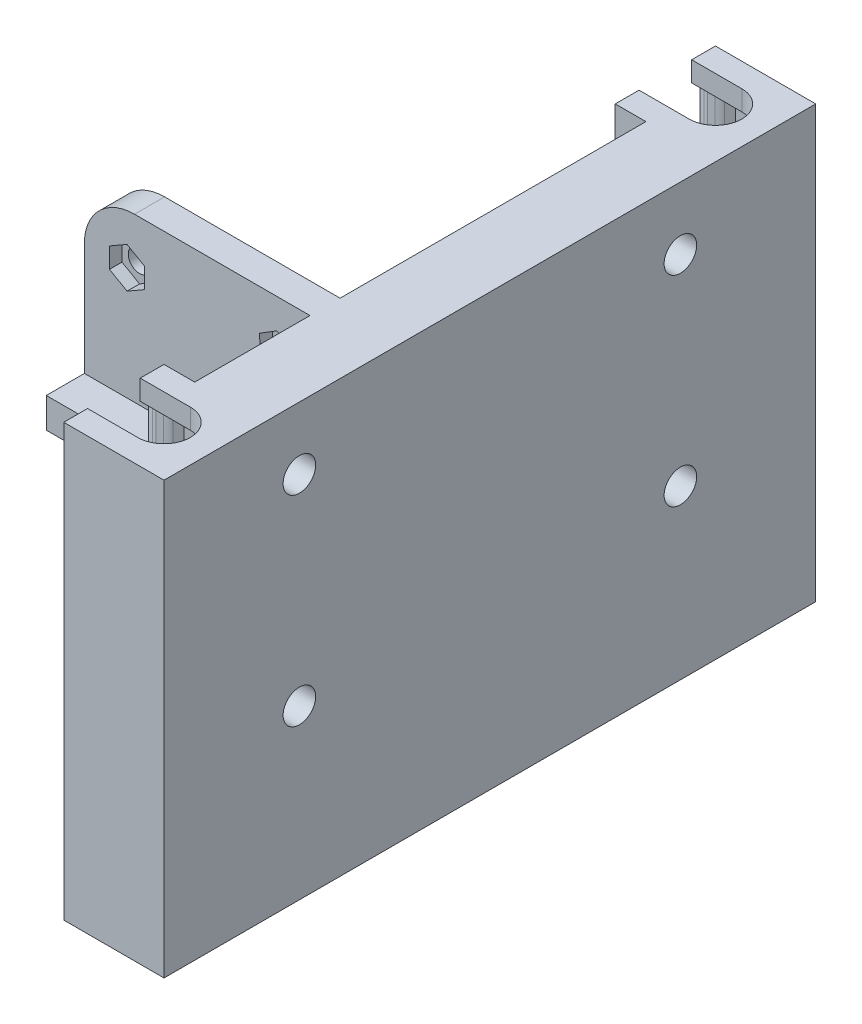
SolidWorks part; units mm, degrees
ref_plane "Front Plane" through (0, 0, 0) normal (0, 0, 1) x (1, 0, 0)
ref_plane "Top Plane" through (0, 0, 0) normal (0, 1, 0) x (1, 0, 0)
ref_plane "Right Plane" through (0, 0, 0) normal (1, 0, 0) x (0, 0, -1)
sketch "Sketch1" plane through (0, 0, 0) normal (0, 1, 0) x (1, 0, 0)
  line L21 (-7.527, -41.3041) -> (-7.527, 88.6959)
  line L22 (-7.527, 88.6959) -> (-27.527, 88.6959)
  line L23 (-27.527, 88.6959) -> (-27.527, 68.6959)
  line L24 (-27.527, 68.6959) -> (-21.4063, 68.6959)
  line L25 (-21.4063, 68.6959) -> (-21.4063, -21.3041)
  line L26 (-21.4063, -21.3041) -> (-27.527, -21.3041)
  line L27 (-27.527, -21.3041) -> (-27.527, -41.3041)
  line L28 (-27.527, -41.3041) -> (-7.527, -41.3041)
  dimension "D1" = 130
  dimension "D2" = 20
  dimension "D3" = 20
extrude "Boss-Extrude1" add sketch "Sketch1" along normal blind 86
sketch "Sketch2" plane through (0, 86, 0) normal (0, 1, 0) x (1, 0, 0)
  line L0 (-17.527, 83.9459) -> (-27.527, 83.9459)
  line L1 (-27.527, 88.6959) -> (-27.527, 68.6959) construction
  line L2 (-17.527, 73.4459) -> (-27.527, 73.4459)
  line L3 (-27.527, 83.9459) -> (-27.527, 73.4459)
  line L4 (-17.527, -26.0541) -> (-27.527, -26.0541)
  line L5 (-27.527, -21.3041) -> (-27.527, -41.3041) construction
  line L6 (-27.527, -26.0541) -> (-27.527, -36.5541)
  line L7 (-27.527, -36.5541) -> (-17.527, -36.5541)
  line L8 (-17.527, -31.3041) -> (-17.527, 105.8048) construction
  line L9 (-27.527, 78.6959) -> (0, 78.6959) construction
  arc A2 (-17.527, -36.5541) -> (-17.527, -26.0541) centre (-17.527, -31.3041) ccw
  arc A3 (-17.527, 73.4459) -> (-17.527, 83.9459) centre (-17.527, 78.6959) ccw
  point P14 (-27.527, 78.6959)
  dimension "D1" = 10.5
  dimension "D2" = 10.5
extrude "Cut-Extrude1" cut sketch "Sketch2" against normal up to next
sketch "Sketch3" plane through (-27.527, 0, 0) normal (-1, 0, 0) x (0, 0, 1)
  line L0 (41.3041, 73.5608) -> (-72.5469, 73.5608) construction
  line L1 (41.3041, 86) -> (41.3041, 0) construction
  line L2 (41.3041, 8.3895) -> (-72.5469, 8.3895) construction
  line L3 (31.3041, 0) -> (31.3041, 89.0163) construction
  line L4 (26.0541, 0) -> (36.5541, 0) construction
  line L5 (-78.6959, 0) -> (-78.6959, 89.0163) construction
  line L6 (-83.9459, 0) -> (-73.4459, 0) construction
  line L8 (38.8041, 8.3895) -> (23.8041, 8.3895)
  line L9 (38.8041, 8.3895) -> (38.8041, 25.5895)
  line L10 (38.8041, 25.5895) -> (23.8041, 25.5895)
  line L11 (23.8041, 8.3895) -> (23.8041, 25.5895)
  point P18 (31.3041, 8.3895)
  dimension "D1" = 15
  dimension "D2" = 17.2
sketch "Sketch4" plane through (0, 0, 0) normal (0, -1, 0) x (1, 0, 0)
  line L0 (-27.527, 24.3841) -> (-27.527, 38.2241)
  line L1 (-21.057, -86.2406) -> (-17.527, -86.2406)
  line L3 (-27.527, 31.3041) -> (-7.2627, 31.3041) construction
  line L4 (-21.057, -71.1759) -> (-17.527, -71.1759)
  line L5 (-27.527, 41.3041) -> (-22.1398, 41.3041) construction
  line L6 (-12.277, -78.6959) -> (-33.0477, -78.6959) construction
  line L7 (-21.057, 23.7841) -> (-17.527, 23.7841)
  line L8 (-21.057, 38.8241) -> (-17.527, 38.8241)
  line L9 (-27.527, -85.6159) -> (-27.527, -71.7759)
  line L10 (-27.527, -85.6159) -> (-25.9269, -84.8407)
  line L20 (-27.527, 38.2241) -> (-25.9493, 37.4352)
  line L21 (-25.0549, 37.2241) -> (-23.5502, 37.2241)
  line L22 (-22.1794, 37.7677) -> (-21.057, 38.8241)
  line L23 (-27.527, 24.3841) -> (-25.9493, 25.1729)
  line L24 (-25.0549, 25.3841) -> (-23.5502, 25.3841)
  line L25 (-22.1794, 24.8405) -> (-21.057, 23.7841)
  line L26 (-25.0549, -84.6406) -> (-23.5502, -84.6406)
  line L27 (-22.1794, -85.1842) -> (-21.057, -86.2406)
  line L28 (-27.527, -71.7759) -> (-25.9493, -72.5648)
  line L29 (-25.0549, -72.7759) -> (-23.5502, -72.7759)
  line L30 (-22.1794, -72.2323) -> (-21.057, -71.1759)
  line L32 (-27.527, 41.3041) -> (-27.527, -72.5469) construction
  arc A1 (-17.527, 23.7841) -> (-17.527, 38.8241) centre (-17.527, 31.3041) ccw
  arc A6 (-25.9493, 37.4352) -> (-25.0549, 37.2241) centre (-25.0549, 39.2241) ccw
  arc A7 (-23.5502, 37.2241) -> (-22.1794, 37.7677) centre (-23.5502, 39.2241) ccw
  arc A8 (-23.5502, 25.3841) -> (-22.1794, 24.8405) centre (-23.5502, 23.3841) cw
  arc A9 (-25.9493, 25.1729) -> (-25.0549, 25.3841) centre (-25.0549, 23.3841) cw
  arc A10 (-17.527, -83.9459) -> (-17.527, -73.4459) centre (-17.527, -78.6959) ccw construction
  arc A11 (-17.527, -86.2406) -> (-17.527, -71.1759) centre (-17.527, -78.7083) ccw
  arc A12 (-25.9493, -72.5648) -> (-25.0549, -72.7759) centre (-25.0549, -70.7759) ccw
  arc A13 (-23.5502, -72.7759) -> (-22.1794, -72.2323) centre (-23.5502, -70.7759) ccw
  arc A14 (-23.5502, -84.6406) -> (-22.1794, -85.1842) centre (-23.5502, -86.6406) cw
  arc A15 (-25.9269, -84.8407) -> (-25.0549, -84.6406) centre (-25.0549, -86.6406) cw
  point P0 (-27.527, -78.6959)
  point P29 (-25.527, -72.7759)
  point P32 (-22.757, -72.7759)
  point P35 (-22.757, -84.6406)
  point P38 (-25.5138, -84.6406)
  point P55 (-25.527, 37.2241)
  point P58 (-22.757, 37.2241)
  point P61 (-22.757, 25.3841)
  point P64 (-25.527, 25.3841)
  dimension "D25" = 2
  dimension "D3" = 6.92
  dimension "D4" = 6.92
  dimension "D17" = 1.6
  dimension "D18" = 1.6
  dimension "D19" = 2
  dimension "D20" = 2
  dimension "D21" = 2.77
  dimension "D22" = 2.77
  dimension "D23" = 1.7
  dimension "D24" = 1.7
extrude "Cut-Extrude2" cut sketch "Sketch4" against normal blind 17.2 from offset 4 offset against normal yes
extrude "Cut-Extrude3" cut sketch "Sketch4<2>" against normal blind 17 from offset 65 offset against normal yes
sketch "Sketch4<2>" plane through (0, 0, 0) normal (0, -1, 0) x (1, 0, 0) same geometry as "Sketch4"
sketch "Sketch5" plane through (-21.4063, 0, 0) normal (1, 0, 0) x (0, 0, -1)
  line L1 (7.6959, 86) -> (-4.3041, 86)
  line L2 (7.6959, 86) -> (7.6959, 15)
  line L3 (7.6959, 15) -> (-4.3041, 15)
  line L4 (-4.3041, 86) -> (-4.3041, 15)
  line L6 (-41.3041, 86) -> (-41.3041, 0) construction
  line L9 (68.6959, 0) -> (-21.3041, 0) construction
  line L10 (68.6959, 86) -> (-21.3041, 86) construction
  dimension "D1" = 12
  dimension "D2" = 37
  dimension "D4" = 15
extrude "Boss-Extrude2" add sketch "Sketch5" against normal blind 45
sketch "Sketch6" plane through (-66.4063, 0, 0) normal (-1, 0, 0) x (0, 0, 1)
  line L0 (4.3041, 15) -> (-7.6959, 15) construction
  line L1 (-1.6959, 15) -> (4.3041, 15)
  line L2 (-1.6959, 15) -> (-1.6959, 86)
  line L3 (-1.6959, 86) -> (4.3041, 86)
  line L4 (4.3041, 15) -> (4.3041, 86)
  line L5 (-7.6959, 86) -> (4.3041, 86) construction
  line L6 (4.3041, 86) -> (4.3041, 15) construction
extrude "Cut-Extrude4" cut sketch "Sketch6" against normal up to surface (45 mm away) up to face at (-21.4063, 46.75, -12.6959)
sketch "Sketch8" plane through (0, 0, -1.6959) normal (0, 0, 1) x (1, 0, 0)
  line L0 (-57.9063, 86) -> (-57.9063, 0) construction
  line L1 (-21.4063, 86) -> (-21.4063, 15) construction
  line L4 (-21.4063, 86) -> (-66.4063, 86) construction
  line L5 (-57.9063, 25) -> (-20.4369, 25) construction
  line L6 (-27.9063, 88.1256) -> (-27.9063, 8.6291) construction
  line L7 (-57.9063, 76) -> (-41.0234, 76) construction
  line L8 (-21.4063, 15) -> (-66.4063, 15) construction
  circle A1 centre (-57.9063, 25) radius 2.25
  circle A2 centre (-57.9063, 76) radius 2.25
  circle A3 centre (-27.9063, 25) radius 2.25
  circle A4 centre (-27.9063, 76) radius 2.25
  dimension "D2" = 4.5
  dimension "D4" = 4.5
  dimension "D5" = 4.5
  dimension "D1" = 10
  dimension "D3" = 10
  dimension "D6" = 6.5
  dimension "D7" = 30
extrude "Cut-Extrude6" cut sketch "Sketch8" against normal up to next
sketch "Sketch9" plane through (-7.527, 0, 0) normal (1, 0, 0) x (0, 0, -1)
  circle A5 centre (61.6959, 33.5) radius 3.25 construction
  circle A6 centre (-14.3041, 33.5) radius 3.25 construction
  circle A7 centre (-14.3041, 73.5) radius 3.25 construction
  circle A8 centre (61.6959, 73.5) radius 3.25 construction
  circle A9 centre (61.6959, 33.5) radius 3.25
  circle A10 centre (-14.3041, 33.5) radius 3.25
  circle A11 centre (-14.3041, 73.5) radius 3.25
  circle A12 centre (61.6959, 73.5) radius 3.25
extrude "Cut-Extrude7" cut sketch "Sketch9" against normal through all
sketch "Sketch10" plane through (0, 0, -7.6959) normal (0, 0, -1) x (-1, 0, 0)
  line L1 (61.4063, 27.0207) -> (57.9063, 29.0415)
  line L2 (57.9063, 29.0415) -> (54.4063, 27.0207)
  line L3 (54.4063, 27.0207) -> (54.4063, 22.9793)
  line L4 (54.4063, 22.9793) -> (57.9063, 20.9585)
  line L5 (57.9063, 20.9585) -> (61.4063, 22.9793)
  line L6 (61.4063, 22.9793) -> (61.4063, 27.0207)
  line L7 (61.4063, 78.0207) -> (57.9063, 80.0415)
  line L8 (57.9063, 80.0415) -> (54.4063, 78.0207)
  line L9 (54.4063, 78.0207) -> (54.4063, 73.9793)
  line L10 (54.4063, 73.9793) -> (57.9063, 71.9585)
  line L11 (57.9063, 71.9585) -> (61.4063, 73.9793)
  line L12 (61.4063, 73.9793) -> (61.4063, 78.0207)
  line L13 (7.527, 0) -> (7.527, 86) construction
  line L14 (24.4063, 22.9793) -> (27.9063, 20.9585)
  line L15 (27.9063, 20.9585) -> (31.4063, 22.9793)
  line L16 (31.4063, 22.9793) -> (31.4063, 27.0207)
  line L17 (31.4063, 27.0207) -> (27.9063, 29.0415)
  line L18 (27.9063, 29.0415) -> (24.4063, 27.0207)
  line L19 (24.4063, 27.0207) -> (24.4063, 22.9793)
  line L20 (21.4063, 15) -> (21.4063, 86) construction
  line L22 (27.796, 71.9601) -> (31.3498, 73.8845)
  line L23 (31.3498, 73.8845) -> (31.4602, 77.9244)
  line L24 (31.4602, 77.9244) -> (28.0166, 80.0399)
  line L25 (28.0166, 80.0399) -> (24.4628, 78.1155)
  line L26 (24.4628, 78.1155) -> (24.3524, 74.0756)
  line L27 (24.3524, 74.0756) -> (27.796, 71.9601)
  circle A0 centre (57.9063, 25) radius 3.5 construction
  circle A1 centre (57.9063, 76) radius 3.5 construction
  circle A2 centre (57.9063, 76) radius 2.25 construction
  circle A3 centre (27.9063, 25) radius 3.5 construction
  circle A4 centre (27.9063, 76) radius 3.5 construction
  circle A5 centre (27.9063, 76) radius 2.25 construction
  point P20 (24.4063, 25)
  dimension "D1" = 7
  dimension "D2" = 7
  dimension "D3" = 7
  dimension "D4" = 7
extrude "Cut-Extrude8" cut sketch "Sketch10" along normal blind 2.5 from surface starting at face at (-25.6563, 76, -1.6959)
fillet "Fillet1" radius 10 2 edges at (-66.4063, 86, -4.6959) (-66.4063, 15, -4.6959)
sketch "Sketch11" plane through (-21.4063, 0, 0) normal (-1, 0, 0) x (0, 0, 1)
  line L0 (-1.6959, 76) -> (-1.6959, 25) construction
  line L1 (5.9153, 53.5) -> (-1.6959, 53.5)
  line L2 (5.9153, 53.5) -> (5.9153, 47.5)
  line L3 (5.9153, 47.5) -> (-1.6959, 47.5)
  line L4 (-1.6959, 53.5) -> (-1.6959, 47.5)
  line L6 (-1.6959, 86) -> (-1.6959, 15) construction
  point P10 (-1.6959, 50.5)
  point P11 (-1.6959, 50.5)
  dimension "D1" = 6
extrude "Boss-Extrude3" add sketch "Sketch11" along normal up to surface (45 mm away) up to face at (-66.4063, 50.5, -4.6959)
